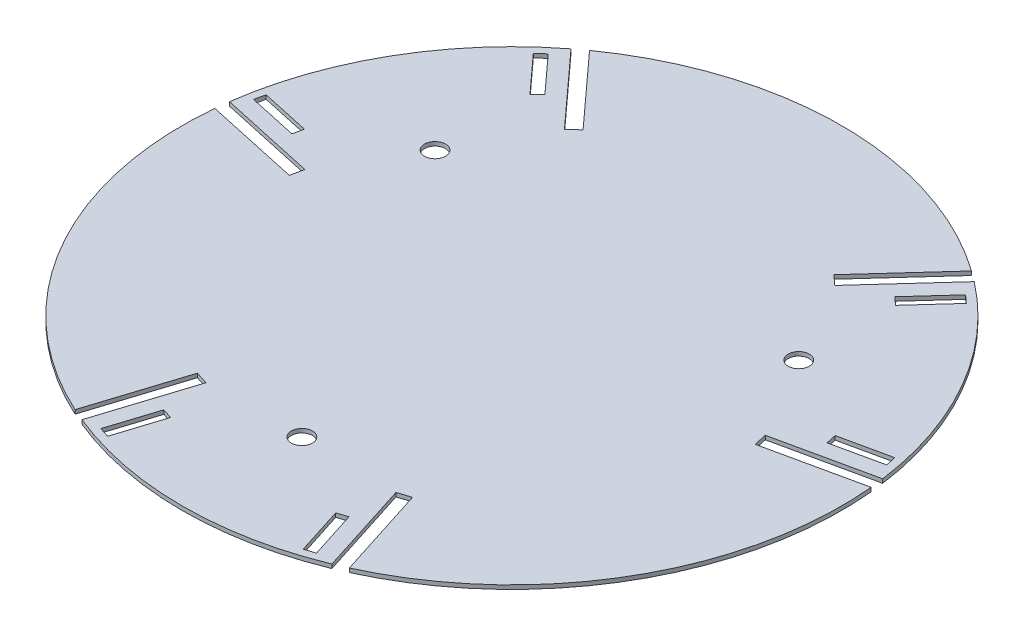
SolidWorks part; units mm, degrees
ref_plane "Front Plane" through (0, 0, 0) normal (0, 0, 1) x (1, 0, 0)
ref_plane "Top Plane" through (0, 0, 0) normal (0, 1, 0) x (1, 0, 0)
ref_plane "Right Plane" through (0, 0, 0) normal (1, 0, 0) x (0, 0, -1)
sketch "Sketch2" plane through (0, 0, 0) normal (0, 1, 0) x (1, 0, 0)
  circle A0 centre (0, 0) radius 125
  dimension "D1" = 250
extrude "Boss-Extrude1" add sketch "Sketch2" along normal blind 1.5 contours A0
sketch "Sketch3" plane through (0, 1.5, 0) normal (0, 1, 0) x (1, 0, 0)
  line L0 (0, 0) -> (-38, -119.084) construction
  line L1 (-270.1917, -358.6733) -> (-267.1917, -358.6733)
  line L2 (-270.1917, -358.6733) -> (-270.1917, -377.6733)
  line L3 (-270.1917, -377.6733) -> (-267.1917, -377.6733)
  line L4 (-267.1917, -358.6733) -> (-267.1917, -377.6733)
  line L9 (-38, -119.084) -> (38, -119.084) construction
  line L10 (0, 0) -> (0, -293.8403) construction
  line L11 (31.312, -98.1252) -> (35.1227, -96.9092)
  line L12 (37.088, -116.226) -> (40.8987, -115.01)
  line L14 (37.088, -116.226) -> (31.312, -98.1252)
  line L15 (40.8987, -115.01) -> (35.1227, -96.9092)
  line L17 (-38, -119.084) -> (-37.088, -116.226) construction
  line L19 (-37.088, -116.226) -> (-31.312, -98.1252)
  line L20 (-37.088, -116.226) -> (-40.8987, -115.01)
  line L21 (-31.312, -98.1252) -> (-35.1227, -96.9092)
  line L22 (-40.8987, -115.01) -> (-35.1227, -96.9092)
  line L52 (-82.1107, 90.2321) -> (-69.3229, 76.1796)
  line L53 (-82.1107, 90.2321) -> (-79.1522, 92.9243)
  line L54 (-79.1522, 92.9243) -> (-66.3645, 78.8717)
  line L55 (-69.3229, 76.1796) -> (-66.3645, 78.8717)
  line L56 (-100.6349, 21.9456) -> (-101.4872, 18.0375)
  line L57 (-120.0509, 22.0857) -> (-101.4872, 18.0375)
  line L58 (-119.1987, 25.9938) -> (-120.0509, 22.0857)
  line L59 (-119.1987, 25.9938) -> (-100.6349, 21.9456)
  line L60 (119.1987, 25.9938) -> (100.6349, 21.9456)
  line L61 (119.1987, 25.9938) -> (120.0509, 22.0857)
  line L62 (120.0509, 22.0857) -> (101.4872, 18.0375)
  line L63 (100.6349, 21.9456) -> (101.4872, 18.0375)
  line L64 (69.3229, 76.1796) -> (66.3645, 78.8717)
  line L65 (79.1522, 92.9243) -> (66.3645, 78.8717)
  line L66 (82.1107, 90.2321) -> (79.1522, 92.9243)
  line L67 (82.1107, 90.2321) -> (69.3229, 76.1796)
  circle A1 centre (0, 0) radius 125 construction
  point P18 (0, 0)
  point P38 (-15.7426, 25.0605)
  point P39 (0, 0)
  point P46 (-7.6333, 12.5317)
  dimension "D1" = 3
  dimension "D2" = 19
  dimension "D3" = 76
  dimension "D4" = 3
  dimension "D5" = 3
  dimension "D7" = 4
  dimension "D8" = 19
extrude "Cut-Extrude1" cut sketch "Sketch3" against normal through all
sketch "Sketch4" plane through (0, 1.5, 0) normal (0, 1, 0) x (1, 0, 0)
  circle A0 centre (0, -79.6391) radius 4
  circle A1 centre (-68.9695, 39.8196) radius 4
  circle A2 centre (68.9695, 39.8196) radius 4
  point P8 (0, 0)
  dimension "D1" = 3
extrude "Cut-Extrude2" cut sketch "Sketch4" against normal through all
sketch "Sketch5" plane through (0, 1.5, 0) normal (0, 1, 0) x (1, 0, 0)
  line L0 (-40.8987, -115.01) -> (-46.6147, -113.186) construction
  line L1 (-35.1227, -96.9092) -> (-40.8987, -115.01) construction
  line L2 (0, -79.6391) -> (0, -151.5792) construction
  line L7 (-46.6147, -113.186) -> (-54.6584, -138.3931) construction
  line L8 (-54.6584, -138.3931) -> (-59.4217, -136.8731) construction
  line L9 (-54.6584, -138.3931) -> (-59.4217, -136.8731)
  line L10 (-54.6584, -138.3931) -> (-36.024, -79.9968)
  line L11 (-59.4217, -136.8731) -> (-40.7873, -78.4768)
  line L12 (-36.024, -79.9968) -> (-40.7873, -78.4768)
  line L13 (59.4217, -136.8731) -> (40.7873, -78.4768)
  line L14 (36.024, -79.9968) -> (40.7873, -78.4768)
  line L15 (54.6584, -138.3931) -> (36.024, -79.9968)
  line L16 (54.6584, -138.3931) -> (59.4217, -136.8731)
  dimension "D1" = 6
  dimension "D2" = 5
extrude "Cut-Extrude4" cut sketch "Sketch5" against normal through all
pattern_circular "CirPattern1" count 3 over 360 about axis through (0, 1.5, 0) along (0, 1, 0) of "Cut-Extrude4"
